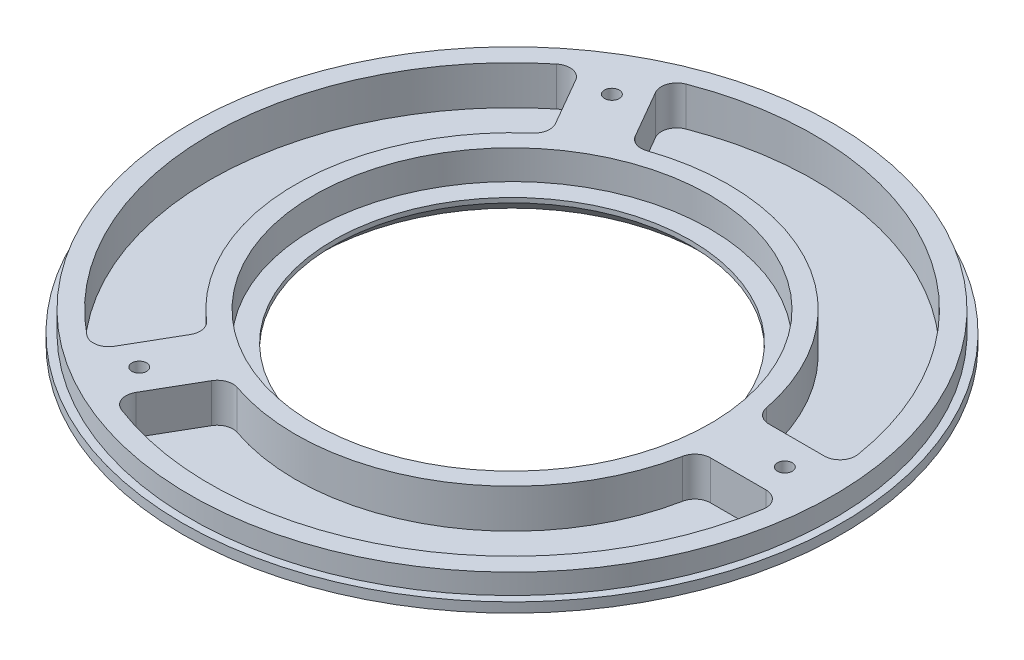
SolidWorks part; units mm, degrees
material "6061-T6 (SS)"
ref_plane "Front Plane" through (0, 0, 0) normal (0, 0, 1) x (1, 0, 0)
ref_plane "Top Plane" through (0, 0, 0) normal (0, 1, 0) x (1, 0, 0)
ref_plane "Right Plane" through (0, 0, 0) normal (1, 0, 0) x (0, 0, -1)
sketch "Sketch2" plane through (0, 0, 0) normal (1, 0, 0) x (0, 0, -1)
  line L0 (-45.8, 0) -> (-82.55, 0)
  line L1 (-82.55, 0) -> (-82.55, 12.7)
  line L2 (-82.55, 12.7) -> (-50.8, 12.7)
  line L3 (-45.8, 0) -> (-45.8, 5.2)
  line L4 (-45.8, 5.2) -> (-50.8, 5.2)
  line L5 (-50.8, 5.2) -> (-50.8, 12.7)
  line L6 (-80.2166, 12.7) -> (-80.2166, 0) construction
  dimension "D1" = 82.55
  dimension "D2" = 12.7
  dimension "D3" = 50.8
  dimension "D4" = 5
  dimension "D5" = 7.5
ref_axis "Axis1" through (0, -0.635, 0) along (0, 1, 0)
revolve "Revolve1" add sketch "Sketch2" angle 360 about axis through (0, -0.635, 0) along (0, 1, 0)
hole_wizard "#90 (0.0087) Diameter Hole1" positions "Sketch6" profile "Sketch7" hole size "#90" standard "ANSI Inch" end condition through all
sketch "Sketch6" plane through (0, 12.7, 0) normal (0, 1, 0) x (1, 0, 0)
  line L0 (0, 0) -> (-69.8201, 120.932) construction
  line L2 (0, 0) -> (0, 109.0908) construction
  point P0 (-35, 60.6218)
  dimension "D1" = 30
  dimension "D2" = 70
sketch "Sketch7" plane through (-35, 12.7, -60.6218) normal (1, 0, 0) x (0, 0, 1)
  line L0 (0, 0) -> (0, 12.7)
  line L1 (0, 12.7) -> (0.1105, 12.7)
  line L2 (0.1105, 12.7) -> (0.1105, 0)
  line L5 (0.1105, 0) -> (0, 0)
  line L11 (0, -6.35) -> (0, 107.95) construction
  dimension "Thru Hole Dia." = 0.221
  dimension "Thru Hole Depth" = 12.7
pattern_circular "CirPattern3" count 3 over 360 about axis through (0, -0.635, 0) along (0, 1, 0) of "#90 (0.0087) Diameter Hole1"
sketch "Sketch8" plane through (0, 12.7, 0) normal (0, 1, 0) x (1, 0, 0)
  line L4 (0, 0) -> (46.9997, 81.4059) construction
  line L5 (-21.0255, 51.4172) -> (-32.098, 70.5955)
  line L6 (55.0414, 7.5) -> (77.1865, 7.5)
  line L7 (0, 0) -> (-35, 60.6218) construction
  arc A0 (-21.0255, 51.4172) -> (55.0414, 7.5) centre (0, 0) cw
  arc A1 (-32.098, 70.5955) -> (77.1865, 7.5) centre (0, 0) cw
  circle A2 centre (0, 0) radius 82.55 construction
  dimension "D1" = 27
  dimension "D2" = 5
  dimension "D3" = 7.5
  dimension "D4" = 60
extrude "Cut-Extrude1" cut sketch "Sketch8" against normal blind 10
fillet "Fillet1" radius 4 4 edges at (-21.0255, 7.7, -51.4172) (55.0414, 7.7, -7.5) (77.1865, 7.7, -7.5) (-32.098, 7.7, -70.5955)
pattern_circular "CirPattern4" count 3 over 360 about axis through (0, -0.635, 0) along (0, 1, 0) of "Cut-Extrude1", "Fillet1"
chamfer "Chamfer1" distance 4 angle 45 1 edges at (0, 0, -45.8)
sketch "Sketch10" plane through (0, 0, 0) normal (0, -1, 0) x (1, 0, 0)
  circle A0 centre (0, 0) radius 82.55
  circle A1 centre (0, 0) radius 84.55
  circle A2 centre (0, 0) radius 82.55 construction
  dimension "D1" = 2
extrude "Boss-Extrude1" add sketch "Sketch10" against normal blind 7.5
chamfer "Chamfer3" distance 5 angle 60 1 edges at (0, 0, -84.55) first distance on face at (0, 7.5, -84.55)
fillet "Fillet4" radius 5 1 edges at (0, 0, 75.8897)
hole_wizard "CBORE for #6 Binding Head Machine Screw1" positions "Sketch13" profile "Sketch14" counterbore size "#6" standard "ANSI Inch" end condition through all
sketch "Sketch13" plane through (0, 0, 0) normal (0, -1, 0) x (-1, 0, 0)
  point P4 (35, 60.6218)
sketch "Sketch14" plane through (-35, 0, -60.6218) normal (1, 0, 0) x (0, 0, -1)
  line L0 (0, 0) -> (0, 12.7)
  line L1 (0, 12.7) -> (1.8986, 12.7)
  line L3 (1.8986, 12.7) -> (1.8987, 2.2098)
  line L4 (1.8987, 2.2098) -> (3.9688, 2.2098)
  line L5 (3.9688, 2.2098) -> (3.9688, 0)
  line L7 (3.9688, 0) -> (0, 0)
  line L11 (0, -6.35) -> (0, 107.95) construction
  dimension "Thru Hole Dia." = 3.7973
  dimension "Thru Hole Depth" = 12.7
  dimension "C'Bore Dia." = 7.9375
  dimension "C'Bore Depth" = 2.2098
pattern_circular "CirPattern5" count 3 over 360 about axis through (0, -0.635, 0) along (0, 1, 0) of "CBORE for #6 Binding Head Machine Screw1"
equation "\"TubeDiameter\" = 6.500in"
